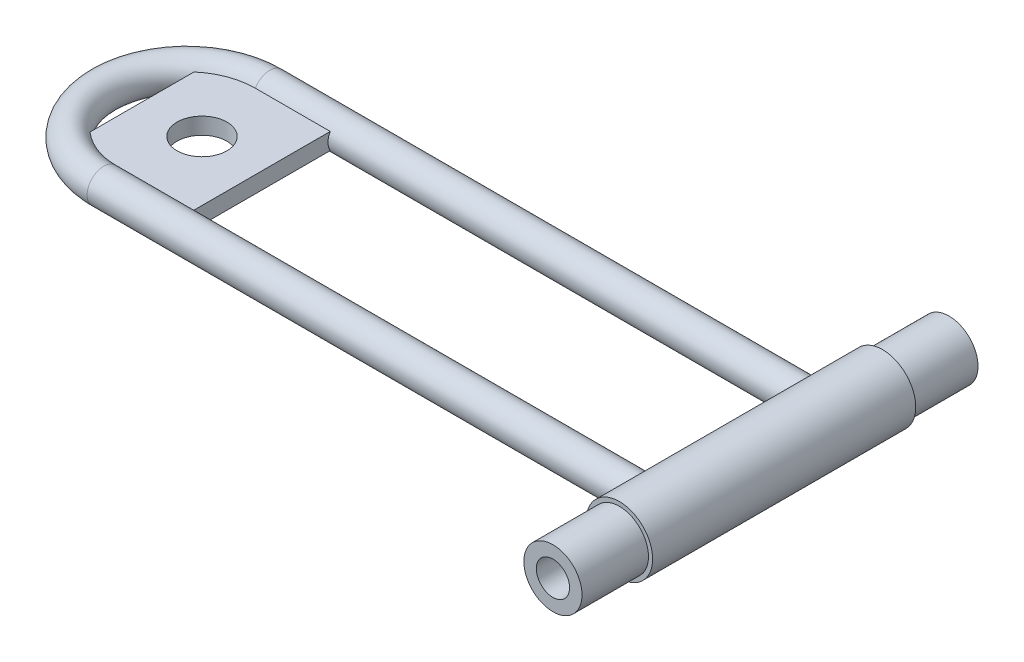
SolidWorks part; units mm, degrees
ref_plane "Front Plane" through (0, 0, 0) normal (0, 0, 1) x (1, 0, 0)
ref_plane "Top Plane" through (0, 0, 0) normal (0, 1, 0) x (1, 0, 0)
ref_plane "Right Plane" through (0, 0, 0) normal (1, 0, 0) x (0, 0, -1)
sketch "Sketch1" plane through (0, 0, 0) normal (0, 0, 1) x (1, 0, 0)
  circle A0 centre (0, 0) radius 6.35
  circle A1 centre (0, 0) radius 3.175
  dimension "D1" = 12.7
  dimension "D2" = 3.175
extrude "Boss-Extrude1" add sketch "Sketch1" along normal blind 62.992
ref_plane "Plane1" through (-3.81, 0, 0) normal (-1, 0, 0) x (0, 0, 1)
sketch "Sketch3" plane through (-3.81, 0, 0) normal (-1, 0, 0) x (0, 0, 1)
  line L0 (0, 0) -> (62.992, 0)
  line L1 (62.992, -6.35) -> (62.992, 6.35) construction
  circle A0 centre (-15.748, 0) radius 3.175
  circle A1 centre (47.244, 0) radius 3.175
  dimension "D3" = 6.35
  dimension "D4" = 6.35
  dimension "D1" = 15.748
  dimension "D2" = 15.748
sketch "Sketch4" plane through (0, 0, 0) normal (0, 1, 0) x (1, 0, 0)
  line L0 (-3.81, -15.6639) -> (-107.95, -15.6639)
  line L1 (-3.81, 0) -> (-3.81, -62.992) construction
  line L2 (-3.81, -47.0944) -> (-107.95, -47.0944)
  line L3 (-6.35, 0) -> (-6.35, -62.992) construction
  arc A0 (-107.95, -15.6639) -> (-107.95, -47.0944) centre (-107.95, -31.3792) ccw
  dimension "D1" = 101.6
sweep "Sweep1" add profiles "Sketch3" path "Sketch4"
ref_plane "Plane2" through (0, 0, 15.24) normal (0, 0, 1) x (1, 0, 0)
sketch "Sketch6" plane through (0, 0, 15.24) normal (0, 0, 1) x (1, 0, 0)
  line L0 (-116.5013, 0) -> (-93.6413, 0)
  line L3 (-93.6413, 0) -> (-116.5013, 0)
  line L4 (-93.6413, 0) -> (-93.6413, -1.5875)
  line L5 (-93.6413, -1.5875) -> (-116.5013, -1.5875)
  line L6 (-116.5013, 0) -> (-116.5013, -1.5875)
  line L7 (-93.6413, 0) -> (-116.5013, 0)
  line L8 (-93.6413, 0) -> (-93.6413, 1.5875)
  line L9 (-93.6413, 1.5875) -> (-116.5013, 1.5875)
  line L10 (-116.5013, 0) -> (-116.5013, 1.5875)
  point P3 (-105.0713, 0)
  dimension "D1" = 22.86
  dimension "D2" = 1.5875
  dimension "D3" = 1.5875
extrude "Boss-Extrude3" add sketch "Sketch6" along normal blind 29.21 contours L0 L6 L5 L4 | L10 L0 L8 L9 region at (-105.0713, 0.7937, 15.24) region at (-105.0713, -0.7937, 15.24)
sketch "Sketch7" plane through (0, 1.5875, 0) normal (0, 1, 0) x (1, 0, 0)
  line L1 (-93.6413, -44.45) -> (-93.6413, -18.2639) construction
  circle A0 centre (-105.0713, -31.3411) radius 4.7625
  dimension "D3" = 9.525
  dimension "D1" = 11.43
  dimension "D2" = 9.906
extrude "Cut-Extrude1" cut sketch "Sketch7" against normal blind 29.21
sketch "Sketch9" plane through (0, 0, 0) normal (0, 0, -1) x (-1, 0, 0)
  circle A0 centre (0, 0) radius 6.35
  circle A1 centre (0, 0) radius 3.175
ref_plane "Plane3" through (0, 0, 31.496) normal (0, 0, 1) x (1, 0, 0)
extrude "Boss-Extrude5" add sketch "Sketch9" along normal blind 6.35
mirror "Mirror1" about plane through (0, 0, 31.496) normal (0, 0, 1) of "Boss-Extrude5"
sketch "Sketch10" plane through (0, 0, 69.342) normal (0, 0, 1) x (1, 0, 0)
  circle A0 centre (0, 0) radius 5.5562
  circle A1 centre (0, 0) radius 6.35
  dimension "D1" = 11.1125
  dimension "D2" = 12.7
extrude "Cut-Extrude6" cut sketch "Sketch10" against normal blind 12.7
sketch "Sketch12" plane through (0, 0, -6.35) normal (0, 0, -1) x (-1, 0, 0)
  circle A0 centre (0, 0) radius 5.5562
  circle A1 centre (0, 0) radius 6.35
  dimension "D1" = 11.1125
extrude "Cut-Extrude7" cut sketch "Sketch12" against normal blind 12.7
